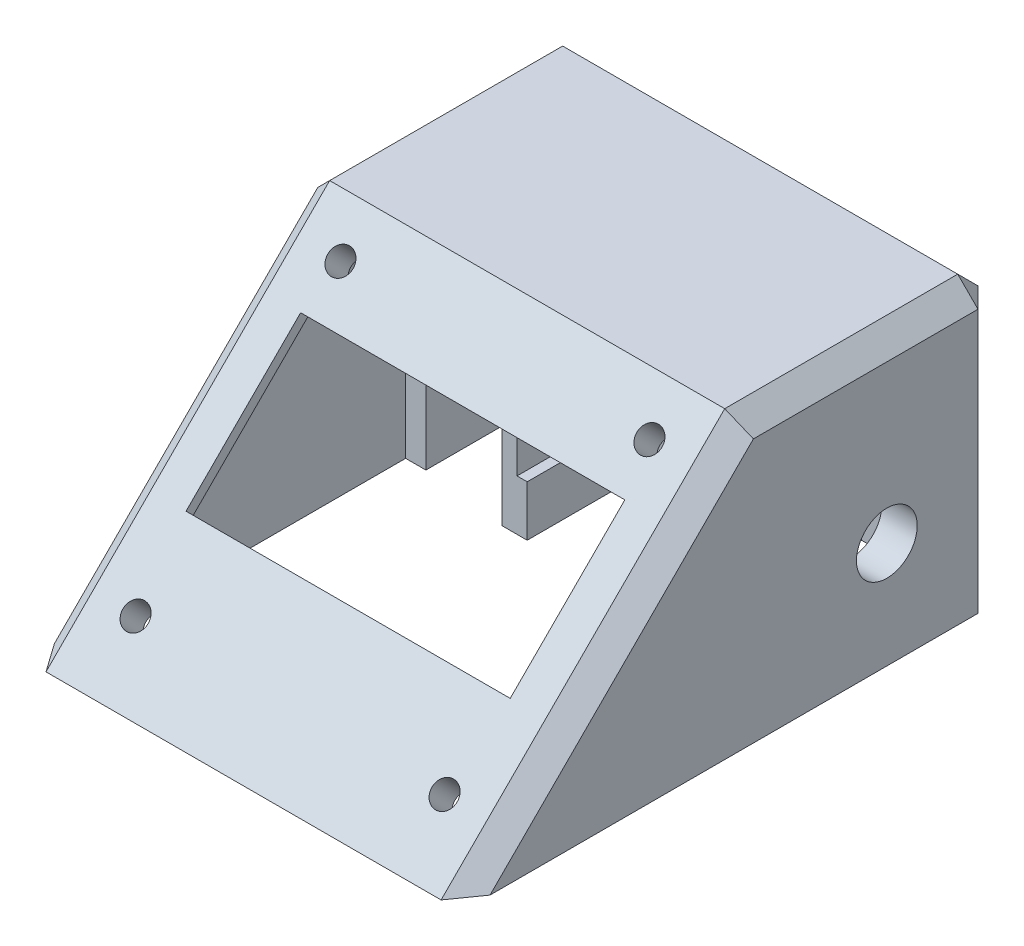
SolidWorks part; units mm, degrees
ref_plane "Front Plane" through (0, 0, 0) normal (0, 0, 1) x (1, 0, 0)
ref_plane "Top Plane" through (0, 0, 0) normal (0, 1, 0) x (1, 0, 0)
ref_plane "Right Plane" through (0, 0, 0) normal (1, 0, 0) x (0, 0, -1)
sketch "Sketch1" plane through (0, 0, 0) normal (1, 0, 0) x (0, 0, -1)
  line L0 (0, 0) -> (26.8701, 26.8701)
  line L1 (26.8701, 26.8701) -> (28.2843, 26.8701)
  line L2 (28.2843, 26.8701) -> (1.4142, 0)
  line L3 (1.4142, 0) -> (0, 0)
  line L4 (1.4142, 0) -> (44.198, 0) construction
  dimension "D1" = 45
  dimension "D2" = 1
  dimension "D3" = 38
extrude "Boss-Extrude1" add sketch "Sketch1" along normal blind 40
sketch "Sketch2" plane through (0, 0, 0) normal (0, 0.7071, 0.7071) x (1, 0, 0)
  line L0 (20, 38) -> (20, 0) construction
  line L1 (40, 38) -> (0, 38) construction
  line L2 (40, 0) -> (0, 0) construction
  line L4 (4, 13) -> (36, 13)
  line L5 (4, 13) -> (4, 29)
  line L6 (4, 29) -> (36, 29)
  line L7 (36, 13) -> (36, 29)
  line L8 (4, 13) -> (36, 29) construction
  line L9 (4, 29) -> (36, 13) construction
  point P6 (20, 21)
  dimension "D1" = 32
  dimension "D2" = 16
  dimension "D3" = 9
extrude "Cut-Extrude1" cut sketch "Sketch2" against normal blind 40
sketch "Sketch3" plane through (0, -0.7071, -0.7071) normal (0, -0.7071, -0.7071) x (1, 0, 0)
  line L0 (20, -29) -> (20, -1) construction
  line L1 (36, -29) -> (4, -29) construction
  line L2 (40, -1) -> (0, -1) construction
  line L4 (4.75, -33.5) -> (35.25, -33.5) construction
  line L5 (4.75, -33.5) -> (4.75, -4.9) construction
  line L6 (4.75, -4.9) -> (35.25, -4.9) construction
  line L7 (35.25, -33.5) -> (35.25, -4.9) construction
  line L8 (4.75, -33.5) -> (35.25, -4.9) construction
  line L9 (4.75, -4.9) -> (35.25, -33.5) construction
  circle A0 centre (4.75, -4.9) radius 1.25
  circle A1 centre (35.25, -4.9) radius 1.25
  circle A2 centre (35.25, -33.5) radius 1.25
  circle A3 centre (4.75, -33.5) radius 1.25
  circle A4 centre (4.75, -33.5) radius 2.5
  circle A5 centre (35.25, -33.5) radius 2.5
  circle A6 centre (35.25, -4.9) radius 2.5
  circle A7 centre (4.75, -4.9) radius 2.5
  point P6 (20, -19.2)
  dimension "D4" = 2.5
  dimension "D5" = 5
  dimension "D1" = 28.6
  dimension "D2" = 30.5
  dimension "D3" = 4.5
extrude "Boss-Extrude2" add sketch "Sketch3" along normal blind 2.2
extrude "Cut-Extrude2" cut sketch "Sketch3<2>" against normal blind 2.2 contours A0 | A1 | A2 | A3 region at (4.75, 2.7577, -4.1719) region at (35.25, 2.7577, -4.1719) region at (35.25, 22.981, -24.3952) region at (4.75, 22.981, -24.3952)
sketch "Sketch3<2>" plane through (0, -0.7071, -0.7071) normal (0, -0.7071, -0.7071) x (1, 0, 0) same geometry as "Sketch3"
sketch "Sketch4" plane through (40, 0, 0) normal (1, 0, 0) x (0, 0, -1)
  line L0 (0, 0) -> (-1.1299, -1.1299)
  line L1 (26.8701, 26.8701) -> (51.8701, 26.8701)
  line L2 (26.8701, 26.8701) -> (26.8701, 25.3701)
  line L3 (26.8701, 25.3701) -> (51.8701, 25.3701)
  line L4 (51.8701, 26.8701) -> (51.8701, 25.3701)
  line L5 (51.8701, 26.8701) -> (50.3701, 26.8701)
  line L6 (51.8701, 26.8701) -> (51.8701, -1.1299)
  line L7 (51.8701, -1.1299) -> (50.3701, -1.1299)
  line L8 (50.3701, 26.8701) -> (50.3701, -1.1299)
  line L9 (-1.1299, -1.1299) -> (0.2843, -1.1299)
  line L10 (0.2843, -1.1299) -> (1.4142, 0)
  line L11 (1.4142, 0) -> (0, 0)
  line L12 (0.2843, -1.1299) -> (50.3701, -1.1299) construction
  line L13 (1.4142, 0) -> (28.2843, 26.8701) construction
  line L14 (26.8701, 26.8701) -> (0, 0) construction
  line M10 (0, 0) -> (1.4142, 0)
  line M11 (1.4142, 0) -> (28.2843, 26.8701)
  dimension "D1" = 1.5
  dimension "D2" = 1.5
  dimension "D3" = 25
  dimension "D4" = 28
extrude "Boss-Extrude3" add sketch "Sketch4" against normal up to surface (40 mm away) contours L8 L1 L2 L3 M11 | L1 L8 L3 L4 | L3 L8 L7 L6 | L9 L10 L0 M10 region at (40, -0.565, -0.1421) region at (40, 26.1119, -38.9494) region at (40, 26.1201, -51.1201) region at (40, 12.1201, -51.1201) up to face at (0, 13.435, -14.1421)
sketch "Sketch5" plane through (40, 0, 0) normal (1, 0, 0) x (0, 0, -1)
  line L0 (51.8701, -1.1299) -> (50.3701, -1.1299) construction
  line L1 (51.8701, 26.8701) -> (51.8701, -1.1299) construction
  line L2 (51.8701, 26.8701) -> (26.8701, 26.8701) construction
  line L3 (26.8701, 26.8701) -> (-1.1299, -1.1299) construction
  line L4 (51.8701, -1.1299) -> (-1.1299, -1.1299)
  line L5 (51.8701, 26.8701) -> (51.8701, -1.1299)
  line L6 (51.8701, 26.8701) -> (26.8701, 26.8701)
  line L7 (26.8701, 26.8701) -> (-1.1299, -1.1299)
extrude "Boss-Extrude4" add sketch "Sketch5" along normal blind 1.5
sketch "Sketch6" plane through (0, 0, 0) normal (-1, 0, 0) x (0, 0, 1)
  line L4 (-51.8701, -1.1299) -> (1.1299, -1.1299)
  line L5 (1.1299, -1.1299) -> (-26.8701, 26.8701)
  line L6 (-26.8701, 26.8701) -> (-51.8701, 26.8701)
  line L7 (-51.8701, 26.8701) -> (-51.8701, -1.1299)
  line L8 (-51.8701, -1.1299) -> (1.1299, -1.1299)
  line L9 (1.1299, -1.1299) -> (-26.8701, 26.8701)
  line L10 (-26.8701, 26.8701) -> (-51.8701, 26.8701)
  line L11 (-51.8701, 26.8701) -> (-51.8701, -1.1299)
  dimension "D1" = 0
extrude "Boss-Extrude5" add sketch "Sketch6" along normal blind 1.5
sketch "Sketch7" plane through (0, 0, -51.8701) normal (0, 0, -1) x (-1, 0, 0)
  line L0 (1.5, -1.1299) -> (-41.5, -1.1299) construction
  line L1 (-27, -9.1299) -> (-13, -9.1299)
  line L2 (-27, -9.1299) -> (-27, 6.8701)
  line L3 (-27, 6.8701) -> (-13, 6.8701)
  line L4 (-13, -9.1299) -> (-13, 6.8701)
  line L5 (-27, -9.1299) -> (-13, 6.8701) construction
  line L6 (-27, 6.8701) -> (-13, -9.1299) construction
  line L8 (-28, 3.8701) -> (-12, 3.8701)
  line L9 (-28, 3.8701) -> (-28, 9.8701)
  line L10 (-28, 9.8701) -> (-12, 9.8701)
  line L11 (-12, 3.8701) -> (-12, 9.8701)
  line L12 (-28, 3.8701) -> (-12, 9.8701) construction
  line L13 (-28, 9.8701) -> (-12, 3.8701) construction
  point P0 (-20, -1.1299)
  point P7 (-20, 6.8701)
  line M5 (-41.5, -1.1299) -> (1.5, -1.1299)
  dimension "D1" = 14
  dimension "D2" = 16
  dimension "D3" = 5
  dimension "D4" = 6
extrude "Cut-Extrude3" cut sketch "Sketch7" against normal blind 1.5 contours L8 L2 L4 M5 | L2 L8 L4 L3 | L8 L11 L10 L9 L2 L3 L4 region at (20, 1.3701, -51.8701) region at (20, 8.0367, -51.8701) region at (20, 5.3701, -51.8701)
sketch "Sketch8" plane through (0, 0, -50.3701) normal (0, 0, 1) x (1, 0, 0)
  line L0 (-1.5, -1.1299) -> (41.5, -1.1299) construction
  line L1 (10.5, -1.1299) -> (29.5, -1.1299)
  line L2 (10.5, -1.1299) -> (10.5, 25.3701)
  line L3 (10.5, 25.3701) -> (29.5, 25.3701)
  line L4 (29.5, -1.1299) -> (29.5, 25.3701)
  line L5 (20, 26.8701) -> (20, 25.3701) construction
  line L6 (41.5, 26.8701) -> (-1.5, 26.8701) construction
  line L7 (28, 3.8701) -> (28, 9.8701) construction
  line L8 (28, 9.8701) -> (12, 9.8701) construction
  line L9 (28, 9.8701) -> (12, 9.8701)
  line L10 (12, 3.8701) -> (12, 9.8701) construction
  line L11 (12, 3.8701) -> (12, 9.8701)
  line L12 (13, 3.8701) -> (12, 3.8701) construction
  line L13 (13, 3.8701) -> (12, 3.8701)
  line L14 (13, -1.1299) -> (13, 3.8701) construction
  line L15 (13, -1.1299) -> (13, 3.8701)
  line L16 (28, 3.8701) -> (28, 9.8701)
  line L17 (28, 3.8701) -> (27, 3.8701) construction
  line L18 (28, 3.8701) -> (27, 3.8701)
  line L19 (27, -1.1299) -> (27, 3.8701) construction
  line L20 (27, -1.1299) -> (27, 3.8701)
  line L21 (0, 25.3701) -> (40, 25.3701) construction
  line M6 (13, -1.1299) -> (13, 3.8701)
  line M7 (13, 3.8701) -> (12, 3.8701)
  line M8 (12, 3.8701) -> (12, 9.8701)
  line M9 (12, 9.8701) -> (28, 9.8701)
  line M10 (28, 9.8701) -> (28, 3.8701)
  line M11 (28, 3.8701) -> (27, 3.8701)
  line M12 (27, 3.8701) -> (27, -1.1299)
  line M13 (27, -1.1299) -> (40, -1.1299)
  line M15 (40, 25.3701) -> (0, 25.3701)
  line M17 (0, -1.1299) -> (13, -1.1299)
  dimension "D1" = 1.5
extrude "Boss-Extrude6" add sketch "Sketch8" along normal blind 16.5 contours L4 L3 L2 M13 M15 M17 M6 M7 M8 M9 M10 M11 M12 region at (20, 15.843, -50.3701)
sketch "Sketch10" plane through (0, 25.3701, 0) normal (0, -1, 0) x (1, 0, 0)
  line L0 (0, -26.8701) -> (0, -50.3701) construction
  line L1 (0, -34.8701) -> (2, -34.8701)
  line L2 (0, -34.8701) -> (0, -46.8701)
  line L3 (0, -46.8701) -> (2, -46.8701)
  line L4 (2, -34.8701) -> (2, -46.8701)
  line L5 (40, -26.8701) -> (40, -50.3701) construction
  line L6 (40, -34.8701) -> (38, -34.8701)
  line L7 (40, -34.8701) -> (40, -46.8701)
  line L8 (40, -46.8701) -> (38, -46.8701)
  line L9 (38, -34.8701) -> (38, -46.8701)
  line L10 (0, -50.3701) -> (10.5, -50.3701) construction
  dimension "D1" = 2
  dimension "D2" = 12
  dimension "D3" = 3.5
extrude "Boss-Extrude7" add sketch "Sketch10" along normal up to surface (26.5 mm away) up to face at (20, -1.1299, -33.9218)
sketch "Sketch9" plane through (-1.5, 0, 0) normal (-1, 0, 0) x (0, 0, 1)
  line L0 (-51.8701, -1.1299) -> (1.1299, -1.1299) construction
  line L1 (-33.8701, -1.1299) -> (-33.8701, 25.3701) construction
  line L2 (-33.8701, -1.1299) -> (-33.8701, 25.3701) construction
  circle A0 centre (-40.8701, 9.3701) radius 3
  dimension "D1" = 7.5
  dimension "D3" = 6
  dimension "D2" = 7
extrude "Cut-Extrude4" cut sketch "Sketch9" against normal through all
chamfer "Chamfer1" distance 2 angle 45 7 edges at (41.5, 12.8701, -12.8701) (-1.5, 12.8701, -12.8701) (-1.5, 26.8701, -39.3701) (-1.5, 12.8701, -51.8701) (41.5, 12.8701, -51.8701) (20, 26.8701, -51.8701) (41.5, 26.8701, -39.3701)
chamfer "Chamfer2" distance 2 angle 45 8 edges at (40, 25.3701, -48.6201) (34.75, 25.3701, -50.3701) (5.25, 25.3701, -50.3701) (0, 25.3701, -48.6201) (0, 25.3701, -30.8701) (40, 25.3701, -30.8701) (40, 12.163, -13.5772) (0, 12.163, -13.5772)
sketch "Sketch11" plane through (0, 0, -26.8701) normal (0, 0, 1) x (1, 0, 0)
  line L6 (38, 25.3701) -> (38.2071, 25.163)
  line L7 (38.2071, 25.163) -> (38, 25.4558)
  line L8 (38, 25.4558) -> (2, 25.4558)
  line L9 (2, 25.4558) -> (1.7929, 25.163)
  line L10 (1.7929, 25.163) -> (2, 25.3701)
  line L11 (2, 25.3701) -> (38, 25.3701)
  line L12 (38, 25.3701) -> (38.2071, 25.163)
  line L13 (38.2071, 25.163) -> (38, 25.4558)
  line L14 (38, 25.4558) -> (2, 25.4558)
  line L15 (2, 25.4558) -> (1.7929, 25.163)
  line L16 (1.7929, 25.163) -> (2, 25.3701)
  line L17 (2, 25.3701) -> (38, 25.3701)
  dimension "D1" = 0
extrude "Boss-Extrude8" add sketch "Sketch11" along normal blind 1
fillet "Fillet1" radius 5 1 edges at (20, 25.3701, -26.7843)
ref_plane "Plane3" through (20, 0, 0) normal (-1, 0, 0) x (0, 0, 1)
